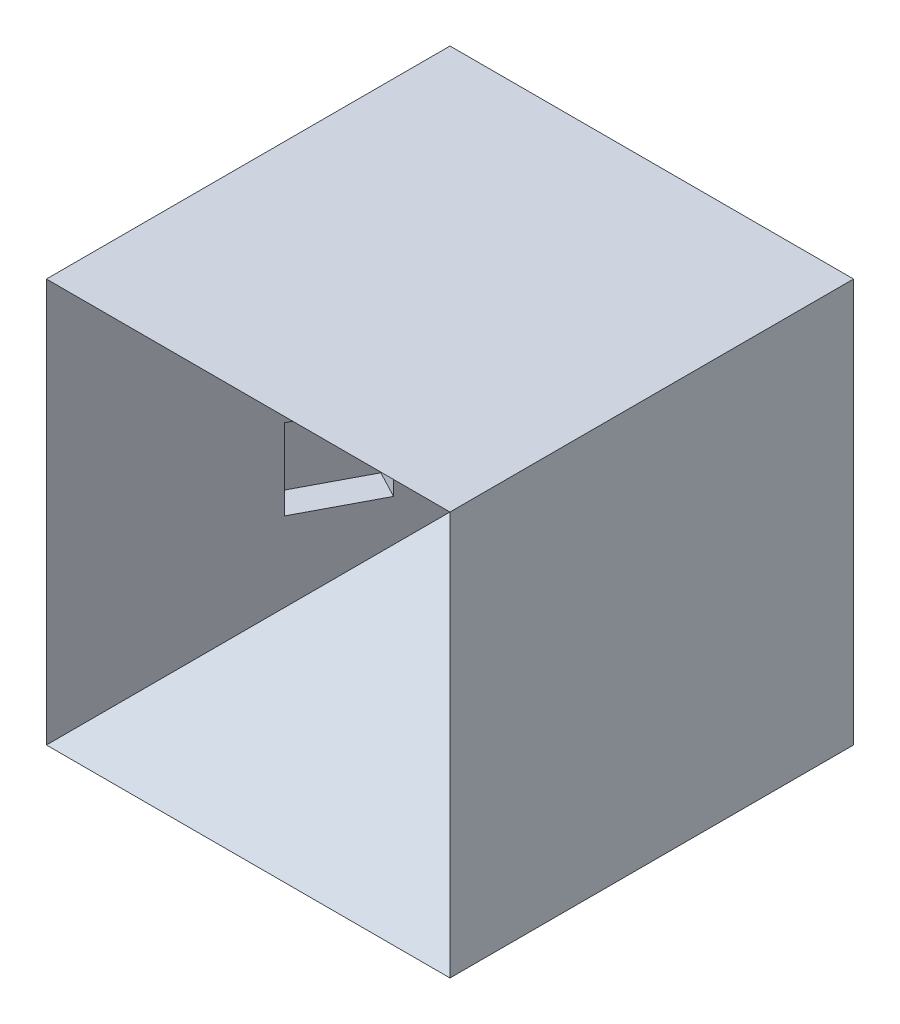
SolidWorks part; units mm, degrees
ref_plane "Front Plane" through (0, 0, 0) normal (0, 0, 1) x (1, 0, 0)
ref_plane "Top Plane" through (0, 0, 0) normal (0, 1, 0) x (1, 0, 0)
ref_plane "Right Plane" through (0, 0, 0) normal (1, 0, 0) x (0, 0, -1)
sketch "Sketch1" plane through (0, 0, 0) normal (0, 0, 1) x (1, 0, 0)
  line L1 (10, -10) -> (-10, -10)
  line L2 (10, -10) -> (10, 10)
  line L3 (10, 10) -> (-10, 10)
  line L4 (-10, -10) -> (-10, 10)
  line L5 (10, -10) -> (-10, 10) construction
  line L6 (10, 10) -> (-10, -10) construction
  point P0 (0, 0)
  dimension "D1" = 20
extrude "Boss-Extrude1" add sketch "Sketch1" along normal blind 20
ref_plane "Plane1" through (0, 0, 1) normal (0, 0, 1) x (1, 0, 0)
ref_plane "Plane2" [suppressed] through (0, 0, 23) normal (0, 0, 1) x (1, 0, 0)
sketch "Sketch5" plane through (0, 0, 1) normal (0, 0, 1) x (1, 0, 0)
  point P0 (0, 0)
sketch "Sketch6" plane through (0, 0, 20) normal (0, 0, 1) x (1, 0, 0)
  line L4 (-10, 10) -> (-10, -10)
  line L5 (-10, -10) -> (10, -10)
  line L6 (10, -10) -> (10, 10)
  line L7 (10, 10) -> (-10, 10)
  line L8 (-10, 10) -> (-10, -10)
  line L9 (-10, -10) -> (10, -10)
  line L10 (10, -10) -> (10, 10)
  line L11 (10, 10) -> (-10, 10)
  dimension "D1" = 0
loft "entrada furo" cut profiles "Sketch6", "Sketch5"
sketch "Sketch8" [suppressed] plane through (0, 0, 23) normal (0, 0, 1) x (1, 0, 0)
  point P0 (0, 0)
sketch "Sketch9" [suppressed] plane through (0, 0, 4) normal (0, 0, 1) x (1, 0, 0)
  line L4 (-10, 10) -> (-10, -10)
  line L5 (-10, -10) -> (10, -10)
  line L6 (10, -10) -> (10, 10)
  line L7 (10, 10) -> (-10, 10)
  line L8 (-10, 10) -> (-10, -10)
  line L9 (-10, -10) -> (10, -10)
  line L10 (10, -10) -> (10, 10)
  line L11 (10, 10) -> (-10, 10)
  dimension "D1" = 0
loft "saida veio" [suppressed] add profiles "Sketch9", "Sketch8"
sketch "Sketch10" [suppressed] plane through (0, 9.4794, 4.9892) normal (0, 0.8849, 0.4657) x (1, 0, 0)
  line L0 (0, -20.3531) -> (0, 1.1178) construction
  line L1 (10, 1.1178) -> (-10, 1.1178) construction
  line L3 (2, -7.6177) -> (-2, -7.6177)
  line L4 (2, -7.6177) -> (2, -11.6177)
  line L5 (2, -11.6177) -> (-2, -11.6177)
  line L6 (-2, -7.6177) -> (-2, -11.6177)
  line L7 (2, -7.6177) -> (-2, -11.6177) construction
  line L8 (2, -11.6177) -> (-2, -7.6177) construction
  point P5 (0, -9.6177)
  dimension "D1" = 4
extrude "Cut-Extrude3" [suppressed] cut sketch "Sketch10" against normal blind 1.5
mirror "Mirror2" [suppressed] about plane through (0, 0, 0) normal (0, 1, 0)
pattern_linear "LPattern2" [suppressed] count 15 spacing 20 of bodies 117 113
sketch "Sketch7" plane through (0.4121, 0, 0.2169) normal (0.8849, 0, 0.4657) x (0.4657, 0, -0.8849)
  line L0 (-0.8849, 0) -> (-22.3558, 0) construction
  line L1 (-22.3558, 10) -> (-22.3558, -10) construction
  line L3 (-9.6204, -2) -> (-13.6204, -2)
  line L4 (-9.6204, -2) -> (-9.6204, 2)
  line L5 (-9.6204, 2) -> (-13.6204, 2)
  line L6 (-13.6204, -2) -> (-13.6204, 2)
  line L7 (-9.6204, -2) -> (-13.6204, 2) construction
  line L8 (-9.6204, 2) -> (-13.6204, -2) construction
  point P5 (-11.6204, 0)
  dimension "D1" = 4
extrude "Cut-Extrude2" cut sketch "Sketch7" against normal blind 1.5
mirror "Mirror1" about plane through (0, 0, 0) normal (1, 0, 0) of "Cut-Extrude2"
pattern_linear "LPattern1" [suppressed] count 15 spacing 20 of bodies 106
combine bodies "Combine1" [suppressed] operation type add bodies to combine 107 108 109 106 125 126 127 128 129 130 136 137 138 139 140
combine bodies "Combine2" [suppressed] operation type add bodies to combine 117 114 115 116 119 121 120 122 123 124 135 134 133 132 131
scale "Scale1" bodies to scale 117 scale about centroid uniform scaling yes scale factor 2
equation "\"comprimento unitario\"= 20"
equation "\"D1@Sketch1\"=\"comprimento unitario\""
equation "\"D1@Sketch7\"=\"comprimento unitario\"/5"
equation "\"D3@LPattern1\"=\"comprimento unitario\""
equation "\"D1@Sketch10\"=\"comprimento unitario\"/5"
equation "\"D3@LPattern2\"=\"comprimento unitario\""
equation "\"D1@Boss-Extrude1\"     = \"comprimento unitario\""
